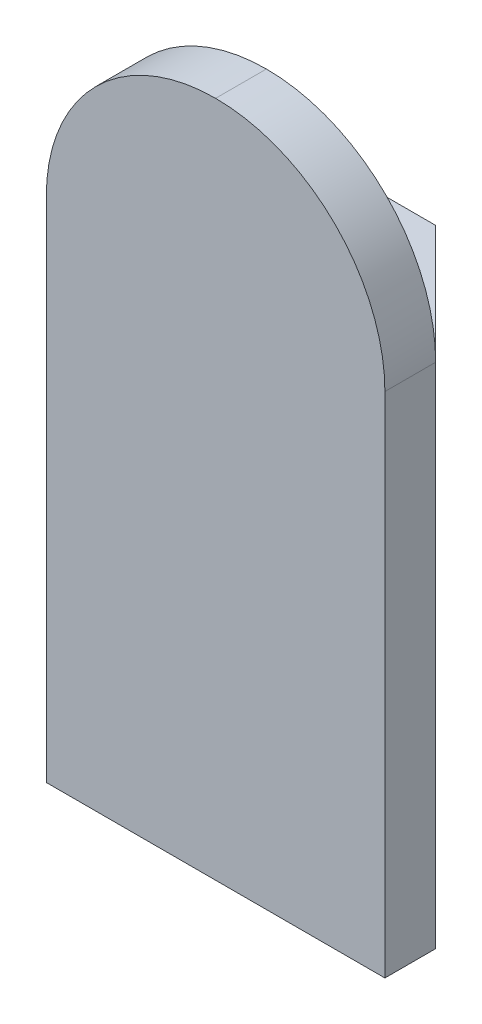
SolidWorks part; units mm, degrees
ref_plane "Спереди" through (0, 0, 0) normal (0, 0, 1) x (1, 0, 0)
ref_plane "Сверху" through (0, 0, 0) normal (0, 1, 0) x (1, 0, 0)
ref_plane "Справа" through (0, 0, 0) normal (1, 0, 0) x (0, 0, -1)
sketch "Эскиз1" plane through (0, 0, 0) normal (0, 1, 0) x (1, 0, 0)
  line L0 (0, 0) -> (0, 20)
  line L1 (0, 20) -> (3, 20)
  line L2 (3, 20) -> (3, 3)
  line L3 (3, 3) -> (20, 3)
  line L4 (20, 3) -> (20, 0)
  line L5 (20, 0) -> (0, 0)
  line L6 (3, 20) -> (20, 3)
  dimension "D1" = 20
  dimension "D2" = 3
extrude "Бобышка-Вытянуть1" add sketch "Эскиз1" along normal mid plane 20 contours L5 L4 L3 L2 L1 L0 region at (0.2828, 0, -10)
extrude "Бобышка-Вытянуть2" add sketch "Эскиз1<3>" along normal blind 3 from offset 10 contours L6 L2 L3 region at (8.6667, 0, -8.6667) offset against normal yes
sketch "Эскиз1<3>" plane through (0, 0, 0) normal (0, 1, 0) x (1, 0, 0) same geometry as "Эскиз1"
mirror "Зеркальное отражение2" about plane through (0, 0, 0) normal (0, 1, 0) of "Бобышка-Вытянуть2"
sketch "Эскиз2" plane through (0, 10, 0) normal (0, 1, 0) x (1, 0, 0)
  line L1 (0, 0) -> (20, 0)
  line L2 (0, 0) -> (0, 3)
  line L3 (0, 3) -> (20, 3)
  line L4 (20, 0) -> (20, 3)
extrude "Бобышка-Вытянуть3" add sketch "Эскиз2" along normal blind 20
fillet "Скругление1" radius 10 2 edges at (0, 30, -1.5) (20, 30, -1.5)
